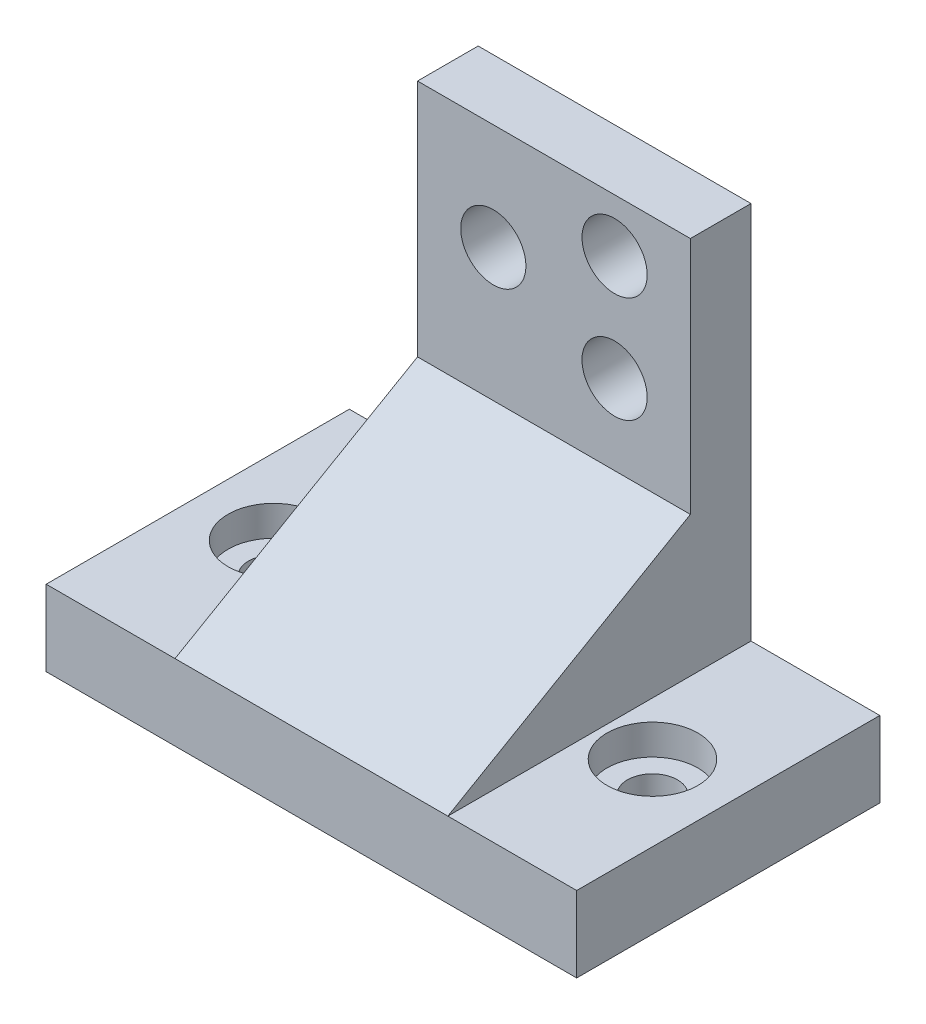
SolidWorks part; units mm, degrees
ref_plane "Front Plane" through (0, 0, 0) normal (0, 0, 1) x (1, 0, 0)
ref_plane "Top Plane" through (0, 0, 0) normal (0, 1, 0) x (1, 0, 0)
ref_plane "Right Plane" through (0, 0, 0) normal (1, 0, 0) x (0, 0, -1)
sketch "Sketch1" plane through (0, 0, 0) normal (0, 1, 0) x (1, 0, 0)
  line L0 (0, 10) -> (0, -10) construction
  line L1 (-17.5, -10) -> (17.5, -10)
  line L2 (-17.5, -10) -> (-17.5, 10)
  line L3 (-17.5, 10) -> (17.5, 10)
  line L4 (17.5, -10) -> (17.5, 10)
  line L5 (-17.5, -10) -> (17.5, 10) construction
  line L6 (-17.5, 10) -> (17.5, -10) construction
  line L7 (-17.5, 0) -> (17.5, 0) construction
  circle A0 centre (-12.5, 0) radius 1.65
  circle A1 centre (12.5, 0) radius 1.65
  point P0 (0, 0)
  dimension "D3" = 3.3
  dimension "D4" = 12.5
  dimension "D1" = 35
  dimension "D2" = 20
extrude "Boss-Extrude1" add sketch "Sketch1" along normal blind 5
sketch "Sketch3" plane through (0, 5, 0) normal (0, 1, 0) x (1, 0, 0)
  line L0 (0, 0) -> (0, 10) construction
  line L1 (17.5, 10) -> (-17.5, 10) construction
  line L3 (-9, 6) -> (9, 6)
  line L4 (-9, 6) -> (-9, 10)
  line L5 (-9, 10) -> (9, 10)
  line L6 (9, 6) -> (9, 10)
  line L7 (-9, 6) -> (9, 10) construction
  line L8 (-9, 10) -> (9, 6) construction
  point P5 (0, 8)
  dimension "D1" = 4
  dimension "D2" = 18
extrude "Boss-Extrude2" add sketch "Sketch3" along normal blind 25
sketch "Sketch4" plane through (0, 0, -6) normal (0, 0, 1) x (1, 0, 0)
  line L0 (-9, 16) -> (9, 16) construction
  line L3 (-9, 30) -> (-9, 5) construction
  line L4 (9, 30) -> (9, 5) construction
  line L5 (-9, 30) -> (9, 30) construction
  line L6 (0, 16) -> (0, 30) construction
  line L7 (0, 23) -> (-9, 23) construction
  circle A0 centre (-4, 23) radius 2.15
  circle A1 centre (4, 26.5) radius 2.15
  circle A2 centre (4, 19.5) radius 2.15
  dimension "D2" = 4.3
  dimension "D3" = 5
  dimension "D4" = 4.3
  dimension "D5" = 8
  dimension "D6" = 3.5
  dimension "D1" = 14
extrude "Cut-Extrude1" cut sketch "Sketch4" against normal up to next
sketch "Sketch5" plane through (0, 5, 0) normal (0, 1, 0) x (1, 0, 0)
  line L0 (0, 6) -> (0, -10) construction
  line L1 (-9, 6) -> (9, 6) construction
  line L2 (-17.5, -10) -> (17.5, -10) construction
  circle A0 centre (-12.5, 0) radius 3
  circle A1 centre (12.5, 0) radius 3
  dimension "D1" = 6
extrude "Cut-Extrude2" cut sketch "Sketch5" against normal blind 2
chamfer "Chamfer1" distance 16 angle 30 1 edges at (0, 5, -6) first distance on face at (-12.5, 5, 3)
